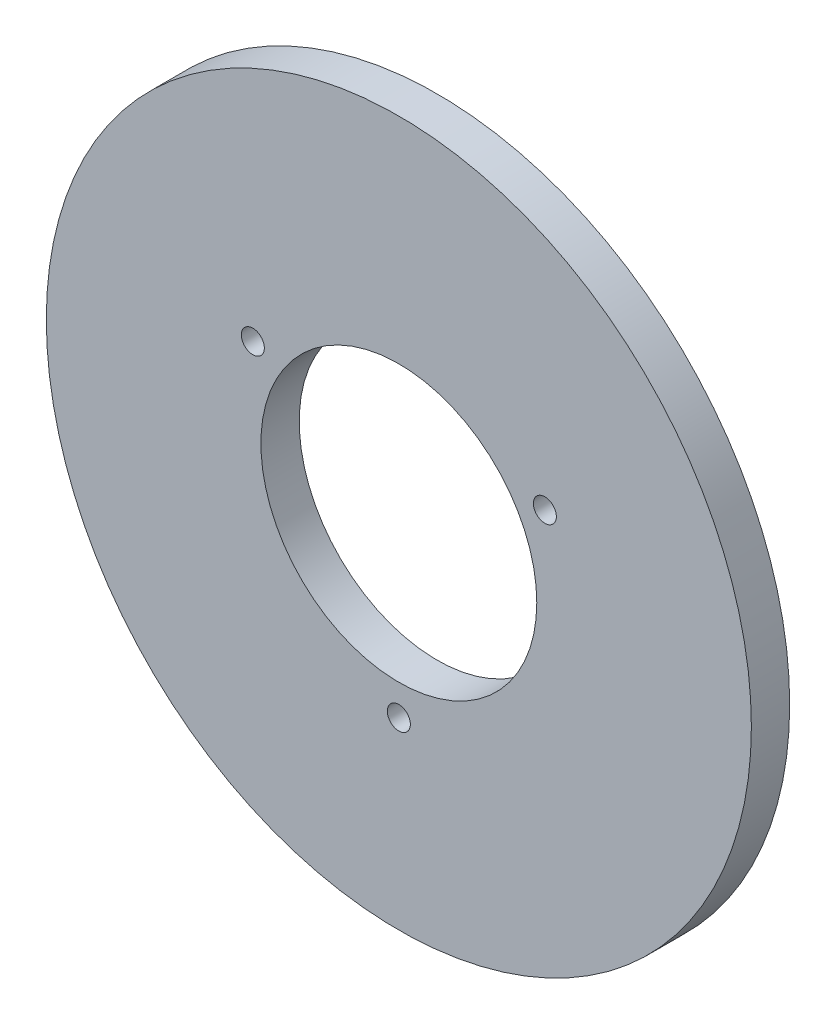
SolidWorks part; units mm, degrees
ref_plane "Front Plane" through (0, 0, 0) normal (0, 0, 1) x (1, 0, 0)
ref_plane "Top Plane" through (0, 0, 0) normal (0, 1, 0) x (1, 0, 0)
ref_plane "Right Plane" through (0, 0, 0) normal (1, 0, 0) x (0, 0, -1)
sketch "Sketch2" plane through (0, 0, 0) normal (0, 0, 1) x (1, 0, 0)
  circle A0 centre (0, 0) radius 46
  circle A2 centre (0, 0) radius 18
  circle A4 centre (0, 0) radius 25 construction
  circle A7 centre (0, -22) radius 1.5
  circle A8 centre (-19.0526, 11) radius 1.5
  circle A11 centre (19.0526, 11) radius 1.5
  point P13 (0, 0)
  dimension "D1" = 36
  dimension "D2" = 92
  dimension "D3" = 3
  dimension "D4" = 3
extrude "Boss-Extrude2" add sketch "Sketch2" along normal blind 5
